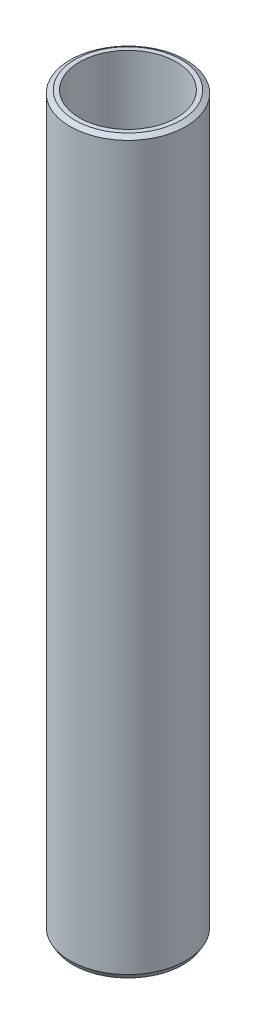
SolidWorks part; units mm, degrees
ref_plane "Front Plane" through (0, 0, 0) normal (0, 0, 1) x (1, 0, 0)
ref_plane "Top Plane" through (0, 0, 0) normal (0, 1, 0) x (1, 0, 0)
ref_plane "Right Plane" through (0, 0, 0) normal (1, 0, 0) x (0, 0, -1)
sketch "Sketch1" plane through (0, 0, 0) normal (0, 1, 0) x (1, 0, 0)
  circle A0 centre (0, 0) radius 47.5
  dimension "SHAFT_OD" = 95
extrude "Boss-Extrude1" add sketch "Sketch1" along normal blind 600
sketch "Sketch2" plane through (0, 0, 0) normal (0, 1, 0) x (1, 0, 0)
  circle A0 centre (0, 0) radius 39.8032
  dimension "BORE_D" = 79.6064
extrude "Cut-Extrude1" cut sketch "Sketch2" along normal through all
chamfer "Chamfer1" distance 2.3529 angle 60 2 edges at (0, 600, 47.5) (0, 0, 47.5) first distance on face at (0, 600, 47.5) first distance on face at (0, 0, 39.8032)
